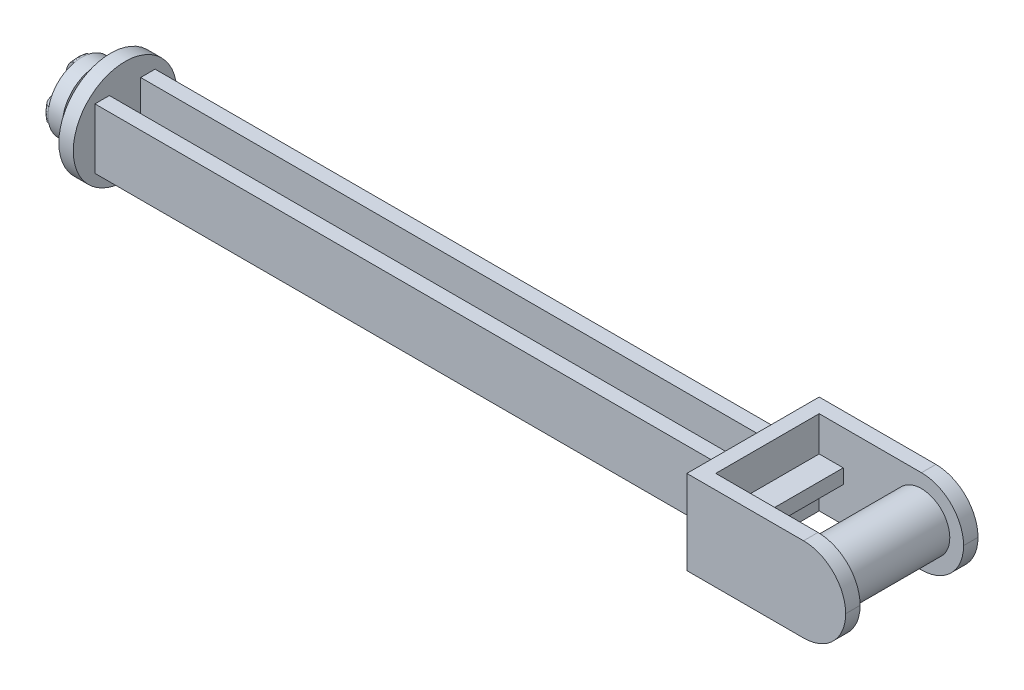
SolidWorks part; units mm, degrees
ref_plane "Front Plane" through (0, 0, 0) normal (0, 0, 1) x (1, 0, 0)
ref_plane "Top Plane" through (0, 0, 0) normal (0, 1, 0) x (1, 0, 0)
ref_plane "Right Plane" through (0, 0, 0) normal (1, 0, 0) x (0, 0, -1)
sketch "Sketch5" plane through (0, 0, 0) normal (1, 0, 0) x (0, 0, -1)
  line L1 (2.5, -2.5) -> (-2.5, -2.5)
  line L2 (2.5, -2.5) -> (2.5, 2.5)
  line L3 (2.5, 2.5) -> (-2.5, 2.5)
  line L4 (-2.5, -2.5) -> (-2.5, 2.5)
  line L5 (2.5, -2.5) -> (-2.5, 2.5) construction
  line L6 (2.5, 2.5) -> (-2.5, -2.5) construction
  point P0 (0, 0)
  dimension "D1" = 5
  dimension "D2" = 5
extrude "Boss-Extrude3" add sketch "Sketch5" along normal blind 52.2
sketch "Sketch6" plane through (0, 0, 0) normal (-1, 0, 0) x (0, 0, 1)
  circle A0 centre (0, 0) radius 4.3
  dimension "D1" = 8.6
extrude "Boss-Extrude4" add sketch "Sketch6" along normal blind 1.2
sketch "Sketch7" plane through (-1.2, 0, 0) normal (-1, 0, 0) x (0, 0, 1)
  line L1 (2, -0.6) -> (-2, -0.6)
  line L2 (2, -0.6) -> (2, 0.6)
  line L3 (2, 0.6) -> (-2, 0.6)
  line L4 (-2, -0.6) -> (-2, 0.6)
  line L5 (2, -0.6) -> (-2, 0.6) construction
  line L6 (2, 0.6) -> (-2, -0.6) construction
  line L7 (0.6, -2) -> (-0.6, -2)
  line L8 (0.6, -2) -> (0.6, 2)
  line L9 (0.6, 2) -> (-0.6, 2)
  line L10 (-0.6, -2) -> (-0.6, 2)
  line L11 (0.6, -2) -> (-0.6, 2) construction
  line L12 (0.6, 2) -> (-0.6, -2) construction
  point P0 (0, 0)
  point P6 (0, 0)
  dimension "D1" = 1.2
  dimension "D2" = 4
extrude "Boss-Extrude5" add sketch "Sketch7" along normal blind 1.2 contours L1 L4 L3 L2 | L10 L9 L8 L7
sketch "Sketch8" plane through (-2.4, 0, 0) normal (-1, 0, 0) x (0, 0, 1)
  circle A0 centre (0, 0) radius 2.8
  dimension "D1" = 5.6
extrude "Boss-Extrude6" add sketch "Sketch8" along normal blind 1.2
sketch "Sketch9" plane through (-3.6, 0, 0) normal (-1, 0, 0) x (0, 0, 1)
  line L1 (2.8, -0.6) -> (-2.8, -0.6)
  line L2 (2.8, -0.6) -> (2.8, 0.6)
  line L3 (2.8, 0.6) -> (-2.8, 0.6)
  line L4 (-2.8, -0.6) -> (-2.8, 0.6)
  line L5 (2.8, -0.6) -> (-2.8, 0.6) construction
  line L6 (2.8, 0.6) -> (-2.8, -0.6) construction
  line L7 (0.6, -2.8) -> (-0.6, -2.8)
  line L8 (0.6, -2.8) -> (0.6, 2.8)
  line L9 (0.6, 2.8) -> (-0.6, 2.8)
  line L10 (-0.6, -2.8) -> (-0.6, 2.8)
  line L11 (0.6, -2.8) -> (-0.6, 2.8) construction
  line L12 (0.6, 2.8) -> (-0.6, -2.8) construction
  circle A0 centre (0, 0) radius 2.8 construction
  point P0 (0, 0)
  point P8 (0, 0)
  circle M1 centre (0, 0) radius 2.8
  dimension "D1" = 1.2
extrude "Boss-Extrude7" add sketch "Sketch9" along normal blind 0.8 contours L10 L3 L8 M1 | L1 L10 L3 M1 | L10 L1 L8 L3 | L10 L8 L1 M1 | L8 L1 L3 M1 region at (-3.6, 0, 1.6893) region at (-3.6, -1.6893, 0) region at (-3.6, 0, 0) region at (-3.6, 0, -1.6893) region at (-3.6, 1.6893, 0)
fillet "Fillet1" radius 0.8 4 edges at (-4.4, 2.8, 0) (-4.4, 0, 2.8) (-4.4, -2.8, 0) (-4.4, 0, -2.8) second distance 1.8 first distance on face at (-4, 0, 0)
sketch "Sketch11" plane through (0, 2.5, 0) normal (0, 1, 0) x (1, 0, 0)
  line L0 (0, 0) -> (52.2, 0) construction
  line L1 (52.2, 2.5) -> (52.2, -2.5) construction
  line L2 (26.1, 0) -> (26.1, -50000) construction
  line L3 (52.2, 2.5) -> (0, 2.5) construction
  line L4 (52.2, -1.3) -> (0, -1.3)
  line L5 (52.2, -1.3) -> (52.2, 1.3)
  line L6 (52.2, 1.3) -> (0, 1.3)
  line L7 (0, -1.3) -> (0, 1.3)
  line L8 (52.2, -1.3) -> (0, 1.3) construction
  line L9 (52.2, 1.3) -> (0, -1.3) construction
  point P7 (26.1, 0)
  point P8 (26.1, 0)
  dimension "D2" = 1.2
extrude "Cut-Extrude1" cut sketch "Sketch11" against normal blind 4
ref_plane "Plane2" through (52.2, 0, 0) normal (1, 0, 0) x (0, 0, -1)
sketch "Sketch12" plane through (52.2, 0, 0) normal (1, 0, 0) x (0, 0, -1)
  line L1 (5.5, -3.5) -> (-5.5, -3.5)
  line L2 (5.5, -3.5) -> (5.5, 3.5)
  line L3 (5.5, 3.5) -> (-5.5, 3.5)
  line L4 (-5.5, -3.5) -> (-5.5, 3.5)
  line L5 (5.5, -3.5) -> (-5.5, 3.5) construction
  line L6 (5.5, 3.5) -> (-5.5, -3.5) construction
  point P0 (0, 0)
  dimension "D1" = 7
  dimension "D2" = 11
extrude "Boss-Extrude8" add sketch "Sketch12" along normal blind 1.2
sketch "Sketch13" plane through (53.4, 0, 0) normal (1, 0, 0) x (0, 0, -1)
  line L0 (-5.5, -3.5) -> (5.5, -3.5) construction
  line L1 (-5.5, 3.5) -> (-4.3, 3.5)
  line L2 (-5.5, 3.5) -> (-5.5, -3.5)
  line L3 (-5.5, -3.5) -> (-4.3, -3.5)
  line L4 (-4.3, 3.5) -> (-4.3, -3.5)
  line L6 (5.5, 3.5) -> (4.3, 3.5)
  line L7 (5.5, 3.5) -> (5.5, -3.5)
  line L8 (5.5, -3.5) -> (4.3, -3.5)
  line L9 (4.3, 3.5) -> (4.3, -3.5)
  dimension "D1" = 1.2
extrude "Boss-Extrude9" add sketch "Sketch13" along normal blind 12
sketch "Sketch14" plane through (53.4, 0, 0) normal (1, 0, 0) x (0, 0, -1)
  line L2 (-4.3, -3.5) -> (-4.3, 3.5) construction
  line L3 (4.3, -0.6) -> (-4.3, -0.6)
  line L4 (4.3, -0.6) -> (4.3, 0.6)
  line L5 (4.3, 0.6) -> (-4.3, 0.6)
  line L6 (-4.3, -0.6) -> (-4.3, 0.6)
  line L7 (4.3, -0.6) -> (-4.3, 0.6) construction
  line L8 (4.3, 0.6) -> (-4.3, -0.6) construction
  point P8 (0, 0)
  dimension "D1" = 1.2
extrude "Boss-Extrude10" add sketch "Sketch14" along normal blind 2
fillet "Fillet2" radius 3.5 4 edges at (65.4, -3.5, 4.9) (65.4, 3.5, 4.9) (65.4, 3.5, -4.9) (65.4, -3.5, -4.9)
sketch "Sketch15" plane through (0, 0, 4.3) normal (0, 0, -1) x (-1, 0, 0)
  line L0 (-61.9, 3.5) -> (-61.9, -49996.5) construction
  circle A0 centre (-61.9, 0) radius 2.3563
  point P5 (0, 0)
extrude "Boss-Extrude11" add sketch "Sketch15" along normal blind 8.6
